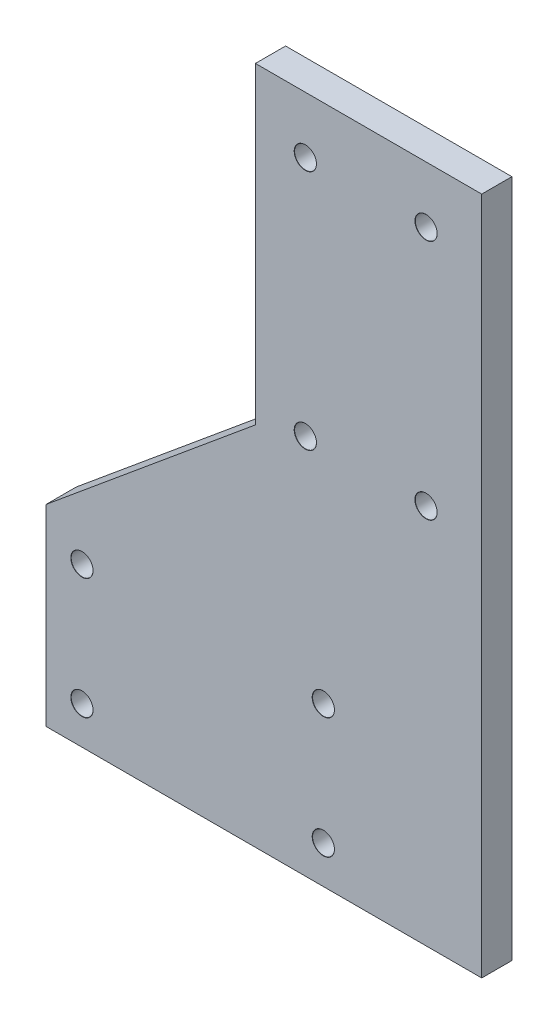
SolidWorks part; units mm, degrees
ref_plane "前视基准面" through (0, 0, 0) normal (0, 0, 1) x (1, 0, 0)
ref_plane "上视基准面" through (0, 0, 0) normal (0, 1, 0) x (1, 0, 0)
ref_plane "右视基准面" through (0, 0, 0) normal (1, 0, 0) x (0, 0, -1)
sketch "草图1" plane through (0, 0, 0) normal (0, 0, 1) x (1, 0, 0)
  line L0 (0, 0) -> (-41.5, 0)
  line L1 (-41.5, 0) -> (-41.5, 25.5)
  line L2 (-41.5, 25.5) -> (-13.75, 48.5)
  line L6 (14.05, -11.5) -> (-49.0563, -11.5) construction
  line L7 (-13.75, 48.5) -> (-13.75, 90)
  line L8 (-13.75, 90) -> (16.25, 90)
  line L9 (16.25, 90) -> (16.25, 0)
  line L10 (-92.1756, 35) -> (57.8057, 35) construction
  line L11 (-105.9645, 43.75) -> (59.2906, 43.75) construction
  line L12 (1.25, -9) -> (1.25, 87.7198) construction
  line L13 (0, 0) -> (16.25, 0)
  dimension "D1" = 41.5
  dimension "D2" = 90
  dimension "D3" = 25.5
  dimension "D4" = 30
  dimension "D5" = 41.5
  dimension "D6" = 35
  dimension "D7" = 8.75
extrude "凸台-拉伸1" add sketch "草图1" along normal blind 4
hole_wizard "M2.5 间隙孔1" positions "草图2" profile "草图3" hole size "M2.5" standard "ISO" end condition through all
sketch "草图2" plane through (0, 0, 4) normal (0, 0, 1) x (1, 0, 0)
  line L0 (-20.75, 0) -> (-20.75, 28.9161) construction
  line L1 (-41.5, 0) -> (16.25, 0) construction
  line L2 (-36.75, 21) -> (-4.75, 21) construction
  line L3 (1.25, 90) -> (1.25, 32.5659) construction
  line L6 (8.8664, 82.5) -> (-7.1336, 82.5) construction
  line L7 (-7.1336, 82.5) -> (-7.1336, 50.5) construction
  line L8 (-7.1336, 50.5) -> (8.8664, 50.5) construction
  line L9 (8.8664, 50.5) -> (8.8664, 82.5) construction
  point P6 (-36.75, 5)
  point P8 (-36.75, 21)
  point P12 (-4.75, 5)
  point P13 (-4.75, 21)
  point P44 (-7.1336, 82.5)
  point P47 (8.8664, 82.5)
  point P51 (-7.1336, 50.5)
  point P54 (8.8664, 50.5)
  dimension "D1" = 16
  dimension "D2" = 16
  dimension "D3" = 0
  dimension "D4" = 5
sketch "草图3" plane through (8.8664, 50.5, 4) normal (1, 0, 0) x (0, -1, 0)
  line L0 (0, 0) -> (0, 4)
  line L1 (0, 4) -> (1.45, 4)
  line L2 (1.45, 4) -> (1.45, 0.025)
  line L3 (1.45, 0.025) -> (1.475, 0)
  line L5 (1.475, 0) -> (0, 0)
  line L6 (-1.45, 0.025) -> (-1.475, 0) construction
  line L11 (0, -6.35) -> (0, 107.95) construction
  dimension "通孔孔直径" = 2.9
  dimension "通孔孔深度" = 4
  dimension "近端锥形沉头孔直径" = 2.95
  dimension "近端锥形沉头孔角度" = 90
